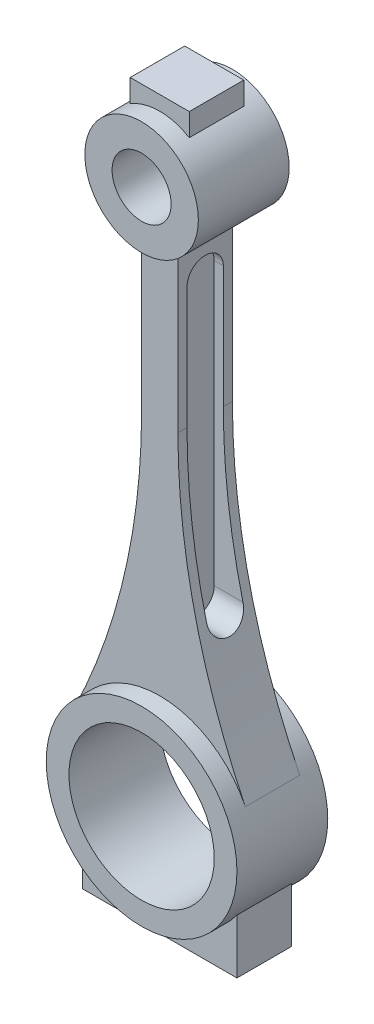
SolidWorks part; units mm, degrees
ref_plane "Front Plane" through (0, 0, 0) normal (0, 0, 1) x (1, 0, 0)
ref_plane "Top Plane" through (0, 0, 0) normal (0, 1, 0) x (1, 0, 0)
ref_plane "Right Plane" through (0, 0, 0) normal (1, 0, 0) x (0, 0, -1)
sketch "Sketch1" plane through (0, 0, 0) normal (0, 0, 1) x (1, 0, 0)
  line L0 (-6.5, 15.6771) -> (6.5, 15.6771)
  line L1 (-6.5, 15.6771) -> (-6.5, 10.6771)
  line L2 (-4, -11.8427) -> (-4, -46.8427)
  line L3 (6.5, 15.6771) -> (6.5, 10.6771)
  line L4 (4, -11.8427) -> (4, -46.8427)
  line L5 (-4, -11.8427) -> (4, -11.8427) construction
  line L6 (0, 0) -> (0, -120) construction
  line L7 (-17, -144.3288) -> (17, -144.3288)
  line L8 (-17, -144.3288) -> (-17, -132.3288)
  line L9 (17, -144.3288) -> (17, -132.3288)
  line L10 (0, -120) -> (-21, -120) construction
  circle A0 centre (0, 0) radius 12.5
  circle A1 centre (0, 0) radius 6.5
  circle A2 centre (0, -120) radius 16
  circle A3 centre (0, -120) radius 21
  arc A5 (-4, -46.8427) -> (-18.8482, -110.7402) centre (-148.9114, -46.8427) cw
  arc A6 (4, -46.8427) -> (18.8482, -110.7402) centre (148.9114, -46.8427) ccw
  point P7 (0, 15.6771)
  point P13 (0, -11.8427)
  point P20 (0, -144.3288)
  dimension "D1" = 13
  dimension "D2" = 25
  dimension "D7" = 32
  dimension "D8" = 42
  dimension "D3" = 5
  dimension "D4" = 13
  dimension "D5" = 8
  dimension "D6" = 35
  dimension "D9" = 120
  dimension "D10" = 34
  dimension "D11" = 12
extrude "Boss-Extrude2" add sketch "Sketch1" along normal mid plane 20 contours A3 A2 | A0 A1 region at (0, 12.1464, 0) region at (0, -99.594, 0)
extrude "Boss-Extrude3" add sketch "Sketch1<6>" along normal mid plane 12 contours A6 L4 A0 L2 A5 A3 | A3 L8 L7 L9 region at (0, -67.5873, 0) region at (0, -141.3606, 0)
sketch "Sketch1<6>" plane through (0, 0, 0) normal (0, 0, 1) x (1, 0, 0) same geometry as "Sketch1"
sketch "Sketch2" plane through (0, 0, 0) normal (0, 0, 1) x (1, 0, 0)
  line L0 (6.5, 15.6771) -> (6.5, 10.6771) construction
  line L1 (-6.5, 15.6771) -> (6.5, 15.6771) construction
  line L2 (-6.5, 15.6771) -> (-6.5, 10.6771) construction
  line L3 (6.5, 15.6771) -> (6.5, 10.6771)
  line L4 (-6.5, 15.6771) -> (6.5, 15.6771)
  line L5 (-6.5, 15.6771) -> (-6.5, 10.6771)
  circle A0 centre (0, 0) radius 12.5 construction
  arc A1 (6.5, 10.6771) -> (-6.5, 10.6771) centre (0, 0) ccw
extrude "Boss-Extrude4" add sketch "Sketch2" along normal mid plane 12
sketch "Sketch3" plane through (4, 0, 0) normal (1, 0, 0) x (0, 0, -1)
  line L0 (0, -82) -> (0, -20) construction
  line L1 (-4, -82) -> (-4, -20)
  line L2 (4, -82) -> (4, -20)
  arc A0 (-4, -82) -> (4, -82) centre (0, -82) ccw
  arc A1 (4, -20) -> (-4, -20) centre (0, -20) ccw
  point P2 (0, -51)
  dimension "D2" = 4
  dimension "D1" = 20
  dimension "D3" = 62
extrude "Cut-Extrude1" cut sketch "Sketch3" against normal through all from offset 6 offset against normal yes
extrude "Cut-Extrude6" cut sketch "Sketch3<5>" along normal through all from offset 2 offset against normal yes
sketch "Sketch3<5>" plane through (4, 0, 0) normal (1, 0, 0) x (0, 0, -1) same geometry as "Sketch3"
